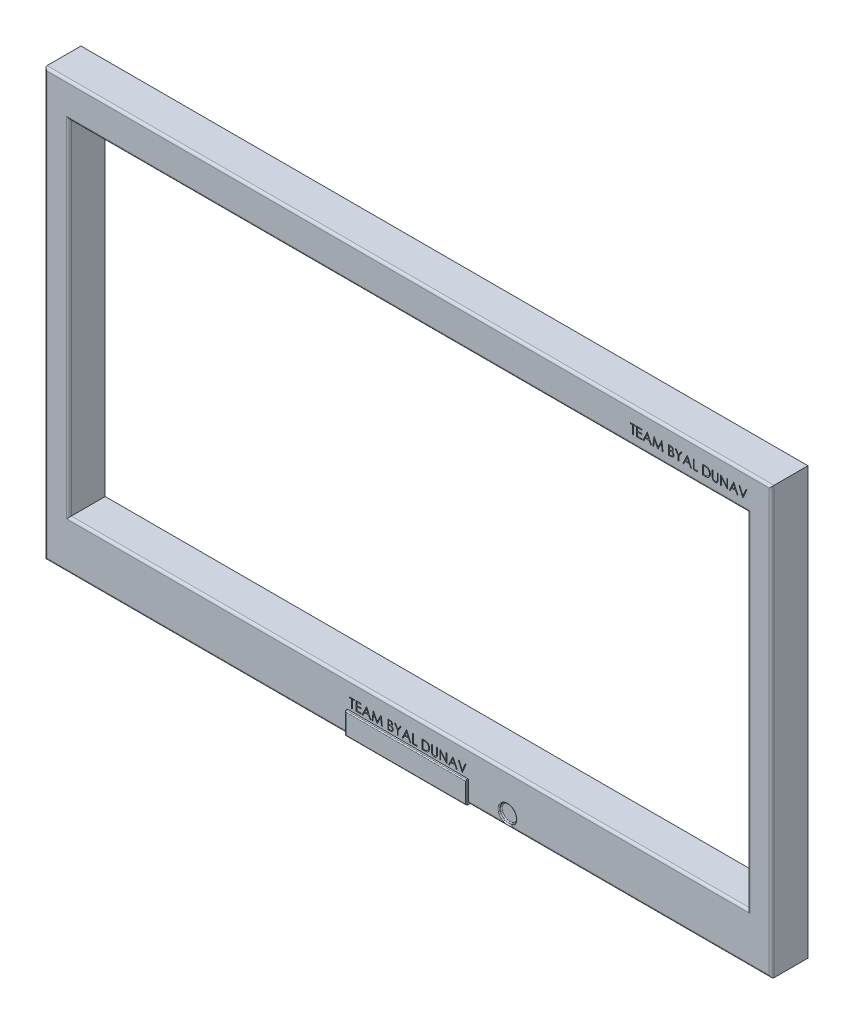
SolidWorks part; units mm, degrees
ref_plane "Front Plane" through (0, 0, 0) normal (0, 0, 1) x (1, 0, 0)
ref_plane "Top Plane" through (0, 0, 0) normal (0, 1, 0) x (1, 0, 0)
ref_plane "Right Plane" through (0, 0, 0) normal (1, 0, 0) x (0, 0, -1)
sketch "Sketch1" plane through (0, 0, 0) normal (0, 0, 1) x (1, 0, 0)
  line L0 (-750, -425) -> (-750, -455)
  line L2 (750, -425) -> (750, 425)
  line L3 (750, 425) -> (-750, 425)
  line L4 (-750, -425) -> (-750, 425)
  line L5 (750, -425) -> (-750, 425) construction
  line L6 (750, 425) -> (-750, -425) construction
  line L7 (700, -355) -> (-700, -355)
  line L8 (700, -355) -> (700, 355)
  line L9 (700, 355) -> (-700, 355)
  line L10 (-700, -355) -> (-700, 355)
  line L11 (700, -355) -> (-700, 355) construction
  line L12 (700, 355) -> (-700, -355) construction
  line L13 (-750, -455) -> (750, -455)
  line L14 (750, -455) -> (750, -425)
  point P0 (0, 0)
  point P6 (0, 0)
  dimension "D1" = 1500
  dimension "D2" = 850
  dimension "D3" = 70
  dimension "D4" = 50
  dimension "D5" = 100
  dimension "D6" = 1400
  dimension "D7" = 710
extrude "Boss-Extrude1" add sketch "Sketch1" along normal blind 75
sketch "Sketch2" plane through (0, 0, 75) normal (0, 0, 1) x (1, 0, 0)
  line L1 (700, 375) -> (-750, 375) construction
  line L4 (750, 425) -> (-750, 425) construction
  line L5 (700, 375) -> (700, 425) construction
  line L7 (-750, 425) -> (-750, -455) construction
  text T0 "TEAM BYAL DUNAV" font "Century Gothic" height in points 72
  dimension "D1" = 50
extrude "Cut-Extrude1" cut sketch "Sketch2" against normal blind 5
sketch "Sketch4" plane through (0, 0, 75) normal (0, 0, 1) x (1, 0, 0)
  line L0 (0, 0) -> (0, -656.1341) construction
  line L1 (-750, -455) -> (750, -455) construction
  line L2 (-125, -455) -> (125, -455)
  line L3 (-125, -455) -> (-125, -410)
  line L4 (-125, -410) -> (125, -410)
  line L5 (125, -455) -> (125, -410)
  line L6 (-125, -455) -> (125, -410) construction
  line L7 (-125, -410) -> (125, -455) construction
  line L8 (-300, -405) -> (300, -405) construction
  line L9 (-385.9201, -432.5) -> (300, -432.5) construction
  circle A0 centre (205, -432.5) radius 17.5
  text T0 "TEAM BYAL DUNAV" font "Century Gothic" height in points 72
  point P7 (0, -432.5)
  dimension "D6" = 80
  dimension "D7" = 35
  dimension "D1" = 250
  dimension "D2" = 45
  dimension "D3" = 50
  dimension "D4" = 300
  dimension "D5" = 300
extrude "Cut-Extrude2" cut sketch "Sketch4" against normal blind 5
sketch "Sketch5" plane through (0, 0, 70) normal (0, 0, 1) x (1, 0, 0)
  line L1 (-125, -410) -> (125, -410)
  line L2 (-125, -410) -> (-125, -455)
  line L3 (-125, -455) -> (125, -455)
  line L4 (125, -410) -> (125, -455)
  line L5 (-125, -410) -> (125, -455) construction
  line L6 (-125, -455) -> (125, -410) construction
  point P4 (0, -432.5)
extrude "Boss-Extrude3" add sketch "Sketch5" along normal blind 10
fillet "Fillet1" radius 5 9 edges at (-437.5, -455, 75) (437.5, -455, 75) (0, -355, 75) (700, 0, 75) (750, -15, 75) (0, 355, 75) (0, 425, 75) (-750, -15, 75) (-700, 0, 75)
fillet "Fillet2" radius 2 4 edges at (0, -410, 80) (125, -432.5, 80) (0, -455, 80) (-125, -432.5, 80)
fillet "Fillet3" radius 2 2 edges at (222.5, -432.5, 75) (222.5, -432.5, 70)
